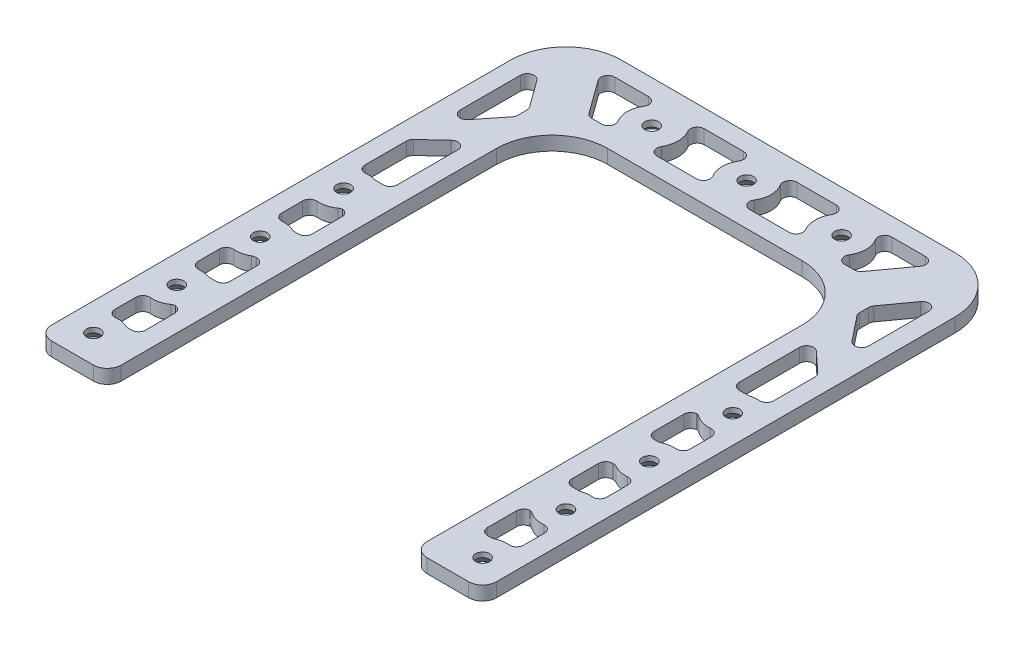
SolidWorks part; units mm, degrees
material "6061-T6 (SS)"
ref_plane "Front Plane" through (0, 0, 0) normal (0, 0, 1) x (1, 0, 0)
ref_plane "Top Plane" through (0, 0, 0) normal (0, 1, 0) x (1, 0, 0)
ref_plane "Right Plane" through (0, 0, 0) normal (1, 0, 0) x (0, 0, -1)
sketch "Sketch1" plane through (0, 0, 0) normal (0, 1, 0) x (1, 0, 0)
  line L0 (-76.2, -114.3) -> (-95.25, -114.3)
  line L1 (-69.85, -107.95) -> (-69.85, 63.5)
  line L2 (-101.6, -107.95) -> (-101.6, 101.6)
  line L3 (76.2, -114.3) -> (95.25, -114.3)
  line L4 (69.85, -107.95) -> (69.85, 63.5)
  line L5 (101.6, -107.95) -> (101.6, 101.6)
  line L6 (-44.45, 88.9) -> (44.45, 88.9)
  line L7 (-76.2, 127) -> (76.2, 127)
  line L8 (-88.9, 12.7) -> (-88.9, -25.4) construction
  line L9 (-88.9, -25.4) -> (-88.9, -63.5) construction
  line L10 (-88.9, -63.5) -> (-88.9, -101.6) construction
  line L11 (-88.9, -101.6) -> (-88.9, -114.3) construction
  line L12 (88.9, 12.7) -> (88.9, -25.4) construction
  line L13 (88.9, -25.4) -> (88.9, -63.5) construction
  line L14 (88.9, -63.5) -> (88.9, -101.6) construction
  line L15 (88.9, -101.6) -> (88.9, -114.3) construction
  line L16 (0, 0) -> (0, 88.9) construction
  circle A0 centre (-88.9, -101.6) radius 3.175
  circle A1 centre (-88.9, -63.5) radius 3.175
  circle A2 centre (-88.9, -25.4) radius 3.175
  circle A3 centre (-88.9, 12.7) radius 3.175
  circle A4 centre (88.9, -101.6) radius 3.175
  circle A5 centre (88.9, -63.5) radius 3.175
  circle A6 centre (88.9, -25.4) radius 3.175
  circle A7 centre (88.9, 12.7) radius 3.175
  arc A8 (-76.2, 127) -> (-101.6, 101.6) centre (-76.2, 101.6) ccw
  arc A9 (76.2, 127) -> (101.6, 101.6) centre (76.2, 101.6) cw
  arc A10 (44.45, 88.9) -> (69.85, 63.5) centre (44.45, 63.5) cw
  arc A11 (-44.45, 88.9) -> (-69.85, 63.5) centre (-44.45, 63.5) ccw
  arc A12 (95.25, -114.3) -> (101.6, -107.95) centre (95.25, -107.95) ccw
  arc A13 (69.85, -107.95) -> (76.2, -114.3) centre (76.2, -107.95) ccw
  arc A14 (-69.85, -107.95) -> (-76.2, -114.3) centre (-76.2, -107.95) cw
  arc A15 (-95.25, -114.3) -> (-101.6, -107.95) centre (-95.25, -107.95) cw
  point P0 (-77.8933, -32.1733)
  point P5 (77.8933, -32.1733)
  dimension "D9" = 114.3
  dimension "D10" = 12.7
  dimension "D11" = 31.75
  dimension "D12" = 203.2
  dimension "D21" = 6.35
  dimension "D26" = 25.4
  dimension "D27" = 25.4
  dimension "D28" = 25.4
  dimension "D29" = 25.4
  dimension "D30" = 6.35
  dimension "D31" = 6.35
  dimension "D32" = 6.35
  dimension "D4" = 38.1
  dimension "D5" = 114.3
  dimension "D6" = 12.7
  dimension "D7" = 38.1
  dimension "D8" = 38.1
  dimension "D13" = 12.7
  dimension "D25" = 38.1
extrude "Boss-Extrude1" add sketch "Sketch1" along normal blind 6.35
sketch "Sketch3" plane through (0, 6.35, 0) normal (0, 1, 0) x (1, 0, 0)
  line L0 (78.105, 23.2583) -> (78.105, 61.3405)
  line L1 (78.105, 61.3405) -> (93.345, 47.1701)
  line L2 (93.345, 47.1701) -> (93.345, 22.8848)
  line L3 (101.6, -107.95) -> (101.6, 101.6) construction
  line L4 (41.984, 127) -> (41.984, 88.9) construction
  line L5 (76.2, 127) -> (-76.2, 127) construction
  line L6 (41.984, 107.95) -> (122.6751, 107.95) construction
  line L7 (77.2597, 118.745) -> (61.5912, 97.155)
  line L8 (93.345, 107.6568) -> (78.105, 86.6572)
  line L9 (78.105, 86.6572) -> (78.105, 80.3905)
  line L10 (78.105, 80.3905) -> (93.345, 61.3405)
  line L11 (93.345, 61.3405) -> (93.345, 107.6568)
  line L12 (46.2686, 97.155) -> (61.5912, 97.155)
  line L13 (46.2686, 118.745) -> (77.2597, 118.745)
  line L14 (0, 97.155) -> (0, 0) construction
  line L15 (37.9597, 118.745) -> (2.8933, 118.745)
  line L16 (2.8933, 118.745) -> (2.8933, 97.155) construction
  line L17 (2.8933, 97.155) -> (37.9597, 97.155)
  line L21 (18.6659, 118.745) -> (73.8713, 118.745) construction
  line L22 (73.8713, 118.745) -> (61.5912, 97.155) construction
  line L23 (61.5912, 97.155) -> (48.8912, 97.155) construction
  line L24 (48.8912, 97.155) -> (18.6659, 118.745) construction
  line L25 (-2.7909, 118.745) -> (2.7909, 118.745) construction
  line L26 (2.7909, 118.745) -> (2.7909, 97.155) construction
  line L27 (2.7909, 97.155) -> (-2.7909, 97.155) construction
  line L28 (-2.7909, 97.155) -> (-2.7909, 118.745) construction
  line L29 (78.105, 4.3177) -> (78.105, -15.6304)
  line L36 (93.345, 2.5152) -> (93.345, -15.2152)
  line L37 (93.345, -35.5848) -> (93.345, -53.3152)
  line L39 (78.105, -91.7384) -> (78.105, -114.3) construction
  line L40 (76.2, -114.3) -> (95.25, -114.3) construction
  line L44 (78.105, 4.3177) -> (81.6045, 4.3177)
  line L45 (83.6044, -15.6304) -> (78.105, -15.6304)
  line L46 (82.6247, -34.5711) -> (78.105, -34.5711)
  line L47 (84.9826, -53.1009) -> (78.105, -53.1009)
  line L48 (81.7916, -72.0415) -> (78.105, -72.0415)
  line L49 (78.105, -72.0415) -> (78.105, -91.7384)
  line L52 (78.105, -91.7384) -> (83.6414, -91.7384)
  line L53 (78.105, -34.5711) -> (78.105, -53.1009)
  line L56 (93.345, -73.6848) -> (93.345, -91.346)
  line L61 (78.105, 23.2583) -> (85.4346, 23.2583)
  line L68 (2.7909, 97.155) -> (48.8912, 97.155) construction
  line L69 (61.5912, 97.155) -> (78.105, 97.155) construction
  line L70 (78.105, 97.155) -> (78.105, 86.6572) construction
  line L71 (78.105, 80.3905) -> (78.105, 61.3405) construction
  line L72 (78.105, 23.2583) -> (78.105, 4.3177) construction
  line L73 (78.105, -15.6304) -> (78.105, -34.5711) construction
  line L74 (78.105, -53.1009) -> (78.105, -72.0415) construction
  line L75 (-18.6659, 118.745) -> (-2.7909, 118.745) construction
  line L77 (2.7909, 118.745) -> (18.6659, 118.745) construction
  line L78 (73.8713, 118.745) -> (93.345, 118.745) construction
  line L79 (93.345, 118.745) -> (93.345, 107.6568) construction
  line L80 (0, 118.745) -> (0, 97.155) construction
  line L81 (-44.45, 88.9) -> (44.45, 88.9) construction
  line L82 (2.7909, 118.745) -> (0, 118.745) construction
  line L85 (69.85, 63.5) -> (69.85, -107.95) construction
  line L86 (69.85, -91.7384) -> (78.105, -91.7384) construction
  line L87 (0, 97.155) -> (2.7909, 97.155) construction
  circle A0 centre (43.3754, 107.95) radius 3.175
  arc A1 (46.2686, 118.745) -> (46.2686, 97.155) centre (43.3754, 107.95) cw
  arc A2 (37.9597, 118.745) -> (37.9597, 97.155) centre (43.3754, 107.95) ccw
  circle A3 centre (0, 107.95) radius 3.175
  arc A4 (2.8933, 118.745) -> (2.8933, 97.155) centre (0, 107.95) cw
  arc A5 (81.7916, -72.0415) -> (93.345, -73.6848) centre (88.9, -63.5) ccw
  arc A6 (93.345, -15.2152) -> (83.6044, -15.6304) centre (88.9, -25.4) ccw
  arc A7 (93.345, 22.8848) -> (85.4346, 23.2583) centre (88.9, 12.7) ccw
  arc A9 (81.6045, 4.3177) -> (93.345, 2.5152) centre (88.9, 12.7) ccw
  arc A11 (82.6247, -34.5711) -> (93.345, -35.5848) centre (88.9, -25.4) ccw
  arc A13 (93.345, -91.346) -> (83.6414, -91.7384) centre (88.9, -101.6) ccw
  arc A15 (93.345, -53.3152) -> (84.9826, -53.1009) centre (88.9, -63.5) ccw
  circle A19 centre (88.9, -63.5) radius 3.175 construction
  circle A20 centre (88.9, -25.4) radius 3.175 construction
  circle A21 centre (88.9, 12.7) radius 3.175 construction
  point P28 (0, 127)
  dimension "D28" = 22.225
  dimension "D29" = 22.225
  dimension "D30" = 22.225
  dimension "D5" = 11.176
  dimension "D7" = 6.35
  dimension "D9" = 11.176
  dimension "D10" = 11.176
  dimension "D4" = 8.255
  dimension "D6" = 8.255
  dimension "D8" = 8.255
  dimension "D13" = 19.05
  dimension "D19" = 12.7
  dimension "D20" = 15.875
  dimension "D21" = 15.875
  dimension "D33" = 8.255
extrude "Cut-Extrude1" cut sketch "Sketch3" against normal blind 6.35
fillet "Fillet4" radius 3.175 35 edges at (93.345, 3.175, -107.6568) (81.7916, 3.175, 72.0415) (93.345, 3.175, 35.5848) (93.345, 3.175, -2.5152) (81.6045, 3.175, -4.3177) (78.105, 3.175, -4.3177) (82.6247, 3.175, 34.5711) (78.105, 3.175, 34.5711) (93.345, 3.175, 53.3152) (93.345, 3.175, 15.2152) (93.345, 3.175, -61.3405) (78.105, 3.175, 53.1009) (84.9826, 3.175, 53.1009) (83.6044, 3.175, 15.6304) (85.4346, 3.175, -23.2583) (78.105, 3.175, 15.6304) (78.105, 3.175, -80.3905) (78.105, 3.175, -86.6572) (78.105, 3.175, 91.7384) (83.6414, 3.175, 91.7384) (93.345, 3.175, 91.346) (93.345, 3.175, 73.6848) (78.105, 3.175, 72.0415) (93.345, 3.175, -22.8848) (78.105, 3.175, -23.2583) (78.105, 3.175, -61.3405) (93.345, 3.175, -47.1701) (77.2597, 3.175, -118.745) (46.2686, 3.175, -97.155) (46.2686, 3.175, -118.745) (61.5912, 3.175, -97.155) (37.9597, 3.175, -118.745) (37.9597, 3.175, -97.155) (2.8933, 3.175, -97.155) (2.8933, 3.175, -118.745)
mirror "Mirror1" about plane through (0, 0, 0) normal (1, 0, 0) of "Fillet4", "Cut-Extrude1"
chamfer "Chamfer1" distance 4.0894 angle 41 11 edges at (88.9, 0, 104.775) (88.9, 0, 66.675) (88.9, 0, -9.525) (88.9, 0, 28.575) (-88.9, 0, -9.525) (-88.9, 0, 28.575) (-88.9, 0, 66.675) (-88.9, 0, 104.775) (-43.3754, 0, -104.775) (43.3754, 0, -104.775) (0, 0, -104.775) first distance on face at (88.9, 6.35, 104.775) first distance on face at (88.9, 6.35, 66.675) first distance on face at (88.9, 6.35, -9.525) first distance on face at (88.9, 6.35, 28.575) first distance on face at (-88.9, 6.35, -9.525) first distance on face at (-88.9, 6.35, 28.575) first distance on face at (-88.9, 6.35, 66.675) first distance on face at (-88.9, 6.35, 104.775) first distance on face at (-85.0083, 0, 44.0815) first distance on face at (43.3754, 0, -104.775) first distance on face at (0, 0, -104.775)
